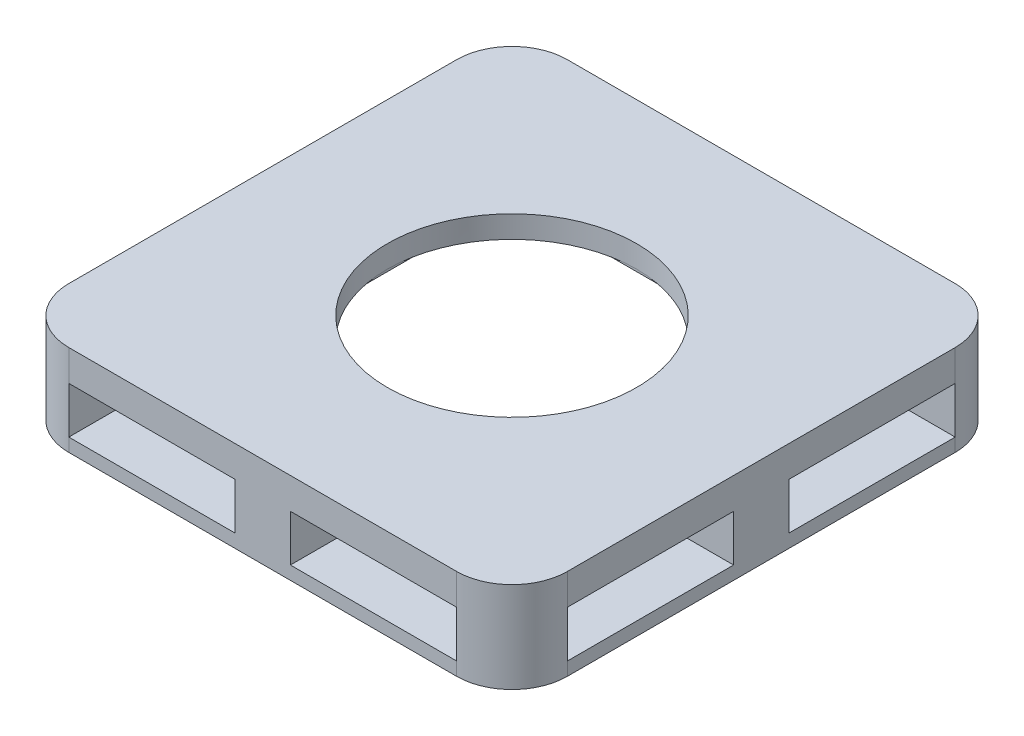
SolidWorks part; units mm, degrees
ref_plane "Plano frontal" through (0, 0, 0) normal (0, 0, 1) x (1, 0, 0)
ref_plane "Plano superior" through (0, 0, 0) normal (0, 1, 0) x (1, 0, 0)
ref_plane "Plano direito" through (0, 0, 0) normal (1, 0, 0) x (0, 0, -1)
sketch "Esboço1" plane through (0, 0, 0) normal (0, 1, 0) x (1, 0, 0)
  line L1 (-22.5, 22.5) -> (22.5, 22.5)
  line L2 (-22.5, 22.5) -> (-22.5, -22.5)
  line L3 (-22.5, -22.5) -> (22.5, -22.5)
  line L4 (22.5, 22.5) -> (22.5, -22.5)
  line L5 (-22.5, 22.5) -> (22.5, -22.5) construction
  line L6 (-22.5, -22.5) -> (22.5, 22.5) construction
  point P0 (0, 0)
  dimension "D2" = 45
  dimension "D3" = 45
extrude "Base" add sketch "Esboço1" along normal blind 1.2
sketch "Esboço2" plane through (0, 1.2, 0) normal (0, 1, 0) x (1, 0, 0)
  line L0 (22.5, -22.5) -> (22.5, 22.5) construction
  line L1 (-22.5, 22.5) -> (-17.5, 22.5)
  line L2 (-22.5, 22.5) -> (-22.5, 17.5)
  line L3 (-22.5, 17.5) -> (-17.5, 17.5)
  line L4 (-17.5, 22.5) -> (-17.5, 17.5)
  line L5 (22.5, 22.5) -> (17.5, 22.5)
  line L6 (22.5, 22.5) -> (22.5, 17.5)
  line L7 (22.5, 17.5) -> (17.5, 17.5)
  line L8 (17.5, 22.5) -> (17.5, 17.5)
  line L9 (22.5, 22.5) -> (-22.5, 22.5) construction
  line L10 (-22.5, 22.5) -> (-22.5, -22.5) construction
  line L11 (22.5, -22.5) -> (17.5, -22.5)
  line L12 (22.5, -22.5) -> (22.5, -17.5)
  line L13 (22.5, -17.5) -> (17.5, -17.5)
  line L14 (17.5, -22.5) -> (17.5, -17.5)
  line L15 (-22.5, -22.5) -> (-17.5, -22.5)
  line L16 (-22.5, -22.5) -> (-22.5, -17.5)
  line L17 (-22.5, -17.5) -> (-17.5, -17.5)
  line L18 (-17.5, -22.5) -> (-17.5, -17.5)
  line L19 (-2.5, 22.5) -> (2.5, 22.5)
  line L20 (-2.5, 22.5) -> (-2.5, 17.5)
  line L21 (-2.5, 17.5) -> (2.5, 17.5)
  line L22 (2.5, 22.5) -> (2.5, 17.5)
  line L23 (-22.5, 2.5) -> (-17.5, 2.5)
  line L24 (-22.5, 2.5) -> (-22.5, -2.5)
  line L25 (-22.5, -2.5) -> (-17.5, -2.5)
  line L26 (-17.5, 2.5) -> (-17.5, -2.5)
  line L27 (-22.5, -22.5) -> (22.5, -22.5) construction
  line L28 (22.5, 2.5) -> (17.5, 2.5)
  line L29 (22.5, 2.5) -> (22.5, -2.5)
  line L30 (22.5, -2.5) -> (17.5, -2.5)
  line L31 (17.5, 2.5) -> (17.5, -2.5)
  line L32 (2.5, -22.5) -> (-2.5, -22.5)
  line L33 (2.5, -22.5) -> (2.5, -17.5)
  line L34 (2.5, -17.5) -> (-2.5, -17.5)
  line L35 (-2.5, -22.5) -> (-2.5, -17.5)
  dimension "D1" = 5
  dimension "D2" = 5
  dimension "D3" = 5
  dimension "D4" = 5
  dimension "D5" = 5
  dimension "D6" = 5
  dimension "D7" = 5
  dimension "D8" = 5
  dimension "D9" = 5
  dimension "D10" = 5
  dimension "D11" = 2.5
  dimension "D12" = 5
  dimension "D13" = 5
  dimension "D14" = 2.5
  dimension "D15" = 5
  dimension "D16" = 5
  dimension "D17" = 2.5
  dimension "D18" = 5
  dimension "D19" = 5
  dimension "D20" = 2.5
extrude "Paredes" add sketch "Esboço2" along normal blind 5
sketch "Esboço3" plane through (0, 6.2, 0) normal (0, 1, 0) x (1, 0, 0)
  line L1 (-22.5, 22.5) -> (22.5, 22.5)
  line L2 (-22.5, 22.5) -> (-22.5, -22.5)
  line L3 (-22.5, -22.5) -> (22.5, -22.5)
  line L4 (22.5, 22.5) -> (22.5, -22.5)
  line L5 (-22.5, 22.5) -> (22.5, -22.5) construction
  line L6 (-22.5, -22.5) -> (22.5, 22.5) construction
  point P0 (0, 0)
extrude "Telhado" add sketch "Esboço3" along normal blind 2
sketch "Esboço4" plane through (0, 1.2, 0) normal (0, 1, 0) x (1, 0, 0)
  line L1 (-12.5, 17.5) -> (12.5, 17.5)
  line L2 (-17.5, 12.5) -> (-17.5, -12.5)
  line L3 (-12.5, -17.5) -> (12.5, -17.5)
  line L4 (17.5, 12.5) -> (17.5, -12.5)
  line L5 (-17.5, 17.5) -> (17.5, -17.5) construction
  line L6 (-17.5, -17.5) -> (17.5, 17.5) construction
  arc A0 (-12.5, -17.5) -> (-17.5, -12.5) centre (-12.5, -12.5) cw
  arc A1 (12.5, -17.5) -> (17.5, -12.5) centre (12.5, -12.5) ccw
  arc A2 (17.5, 12.5) -> (12.5, 17.5) centre (12.5, 12.5) ccw
  arc A3 (-12.5, 17.5) -> (-17.5, 12.5) centre (-12.5, 12.5) ccw
  point P0 (0, 0)
  dimension "D3" = 5
  dimension "D1" = 35
  dimension "D2" = 35
extrude "Corte da Base" cut sketch "Esboço4" against normal blind 2
sketch "Esboço5" plane through (0, 6.2, 0) normal (0, -1, 0) x (1, 0, 0)
  circle A0 centre (0, 0) radius 11.25
  dimension "D1" = 22.5
extrude "Corte do Círculo" cut sketch "Esboço5" against normal blind 2
sketch "Esboço6" plane through (0, 0, -17.5) normal (0, 0, 1) x (1, 0, 0)
  line L0 (22.5, 6.2) -> (22.5, 1.2) construction
  line L1 (17.5, 6.2) -> (22.5, 6.2)
  line L2 (17.5, 6.2) -> (17.5, 5.4)
  line L3 (17.5, 5.4) -> (22.5, 5.4)
  line L4 (22.5, 6.2) -> (22.5, 5.4)
  line L5 (0, -2.995) -> (0, 30.6898) construction
  line L6 (-22.5, 6.2) -> (-22.5, 5.4)
  line L7 (-17.5, 6.2) -> (-22.5, 6.2)
  line L8 (-17.5, 6.2) -> (-17.5, 5.4)
  line L9 (-17.5, 5.4) -> (-22.5, 5.4)
  dimension "D1" = 0.8
extrude "Ponte 1" add sketch "Esboço6" along normal through all
sketch "Esboço7" plane through (17.5, 0, 0) normal (-1, 0, 0) x (0, 0, 1)
  line L0 (17.5, 5.4) -> (2.5, 5.4) construction
  line L1 (22.5, 6.2) -> (17.5, 6.2)
  line L2 (22.5, 6.2) -> (22.5, 5.4)
  line L3 (22.5, 5.4) -> (17.5, 5.4)
  line L4 (17.5, 6.2) -> (17.5, 5.4)
  line L5 (17.5, 5.4) -> (17.5, 1.2) construction
  line L6 (0, -6.5498) -> (0, 26.966) construction
  line L7 (-22.5, 6.2) -> (-22.5, 5.4)
  line L8 (-22.5, 6.2) -> (-17.5, 6.2)
  line L9 (-17.5, 6.2) -> (-17.5, 5.4)
  line L10 (-22.5, 5.4) -> (-17.5, 5.4)
extrude "Ponte 2" add sketch "Esboço7" along normal through all
sketch "Esboço8" plane through (0, 6.2, 0) normal (0, -1, 0) x (-1, 0, 0)
  line L0 (0, 25.395) -> (0, -25.7336) construction
  line L1 (26.4108, 0) -> (-25.8464, 0) construction
  line L2 (-2, -17.5) -> (-17.5, -2)
  line L3 (17.5, -17.5) -> (-17.5, -17.5) construction
  line L4 (-17.5, 17.5) -> (-17.5, -17.5) construction
  line L5 (-2, -17.5) -> (-17.5, -17.5)
  line L6 (-17.5, -17.5) -> (-17.5, -2)
  line L7 (-17.5, 2) -> (-17.5, 17.5)
  line L8 (-17.5, 2) -> (-2, 17.5)
  line L9 (-17.5, 17.5) -> (-2, 17.5)
  line L10 (2, 17.5) -> (17.5, 17.5)
  line L11 (2, 17.5) -> (17.5, 2)
  line L12 (17.5, 17.5) -> (17.5, 2)
  line L13 (17.5, -2) -> (17.5, -17.5)
  line L14 (17.5, -2) -> (2, -17.5)
  line L15 (17.5, -17.5) -> (2, -17.5)
  point P25 (0, 0)
  dimension "D1" = 45
  dimension "D2" = 2
  dimension "D3" = 4
extrude "Ressalto-extrusão6" add sketch "Esboço8" along normal blind 0.4
sketch "Esboço10" plane through (0, 6.2, 0) normal (0, -1, 0) x (1, 0, 0)
  line L0 (-11.25, 8.25) -> (-11.25, -8.25)
  line L1 (-2, -17.5) -> (-17.5, -2) construction
  line L2 (-11.25, 8.25) -> (-17.5, 2)
  line L3 (-17.5, 2) -> (-17.5, -2)
  line L4 (-17.5, -2) -> (-11.25, -8.25)
  line L5 (8.25, 11.25) -> (2, 17.5)
  line L6 (8.25, 11.25) -> (-8.25, 11.25)
  line L7 (-2, 17.5) -> (-8.25, 11.25)
  line L8 (2, 17.5) -> (-2, 17.5)
  line L9 (11.25, -8.25) -> (17.5, -2)
  line L10 (11.25, -8.25) -> (11.25, 8.25)
  line L11 (17.5, 2) -> (11.25, 8.25)
  line L12 (17.5, -2) -> (17.5, 2)
  line L13 (-8.25, -11.25) -> (-2, -17.5)
  line L14 (-8.25, -11.25) -> (8.25, -11.25)
  line L15 (2, -17.5) -> (8.25, -11.25)
  line L16 (-2, -17.5) -> (2, -17.5)
  point P7 (-11.25, 0)
  point P24 (0, 0)
  dimension "D1" = 16.5
  dimension "D2" = 4
extrude "Ressalto-extrusão7" add sketch "Esboço10" along normal blind 0.2
fillet "Filete1" radius 5 1 edges at (-22.5, 4.1, -22.5)
fillet "Filete2" radius 5 1 edges at (-22.5, 4.1, 22.5)
fillet "Filete3" radius 5 1 edges at (22.5, 4.1, 22.5)
fillet "Filete4" radius 5 1 edges at (22.5, 4.1, -22.5)
